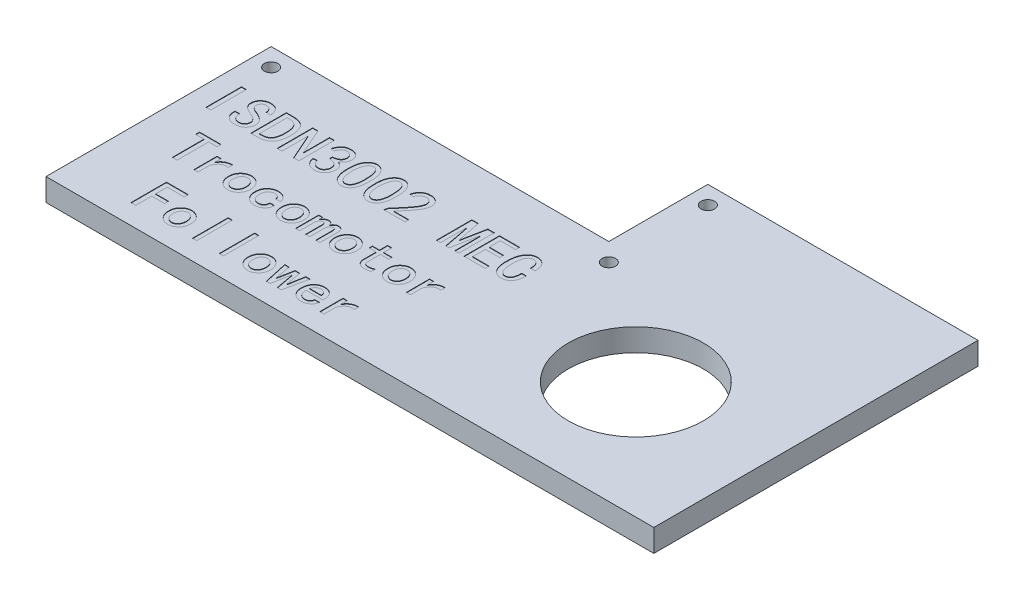
SolidWorks part; units mm, degrees
ref_plane "前视基准面" through (0, 0, 0) normal (0, 0, 1) x (1, 0, 0)
ref_plane "上视基准面" through (0, 0, 0) normal (0, 1, 0) x (1, 0, 0)
ref_plane "右视基准面" through (0, 0, 0) normal (1, 0, 0) x (0, 0, -1)
sketch "Sketch1" plane through (0, 0, 0) normal (0, 1, 0) x (1, 0, 0)
  line L0 (-41.5, -7) -> (33.5, -7)
  line L1 (-37.5, 11) -> (37.5, 11) construction
  line L2 (-37.5, 11) -> (-37.5, -11) construction
  line L3 (-37.5, -11) -> (37.5, -11) construction
  line L4 (37.5, 11) -> (37.5, -11) construction
  line L5 (-37.5, 11) -> (37.5, -11) construction
  line L6 (-37.5, -11) -> (37.5, 11) construction
  line L7 (33.5, -7) -> (33.5, 15)
  line L8 (33.5, 15) -> (93.5, 15)
  line L9 (93.5, 15) -> (93.5, -57)
  line L10 (93.5, -57) -> (-41.5, -57)
  line L11 (-41.5, -57) -> (-41.5, -7)
  line L12 (63.5, 15) -> (63.5, -57) construction
  circle A0 centre (-37.5, -11) radius 1.5
  circle A1 centre (37.5, -11) radius 1.5
  circle A2 centre (37.5, 11) radius 1.5
  circle A3 centre (63.5, -31) radius 15
  point P0 (0, 0)
  dimension "D3" = 3
  dimension "D4" = 3
  dimension "D5" = 3
  dimension "D10" = 20
  dimension "D11" = 30
  dimension "D1" = 22
  dimension "D2" = 75
  dimension "D6" = 4
  dimension "D7" = 4
  dimension "D8" = 4
  dimension "D9" = 4
  dimension "D12" = 30
  dimension "D13" = 30
  dimension "D14" = 50
extrude "Boss-Extrude1" add sketch "Sketch1" along normal blind 5
sketch "Sketch2" plane through (0, 5, 0) normal (0, 1, 0) x (1, 0, 0)
  line L0 (-41.5, -26.1386) -> (33.5, -26.1386) construction
  line L1 (-41.5, -39.5089) -> (33.5, -39.5089) construction
  line L2 (-41.5, -7) -> (-41.5, -57) construction
  line L3 (33.5, -7) -> (33.5, -57) construction
  line L4 (-41.5, -57) -> (93.5, -57) construction
  text T0 "ISDN3002 MEC" font "黑体" height in points 26
  text T1 "Trocomotor\r\nFollower" font "黑体" height in points 26
  point P4 (33.5, -25.9459)
  point P7 (33.5, -42.9432)
  point P13 (-41.5, -43.5005)
extrude "Cut-Extrude1" cut sketch "Sketch2" against normal blind 0.1
